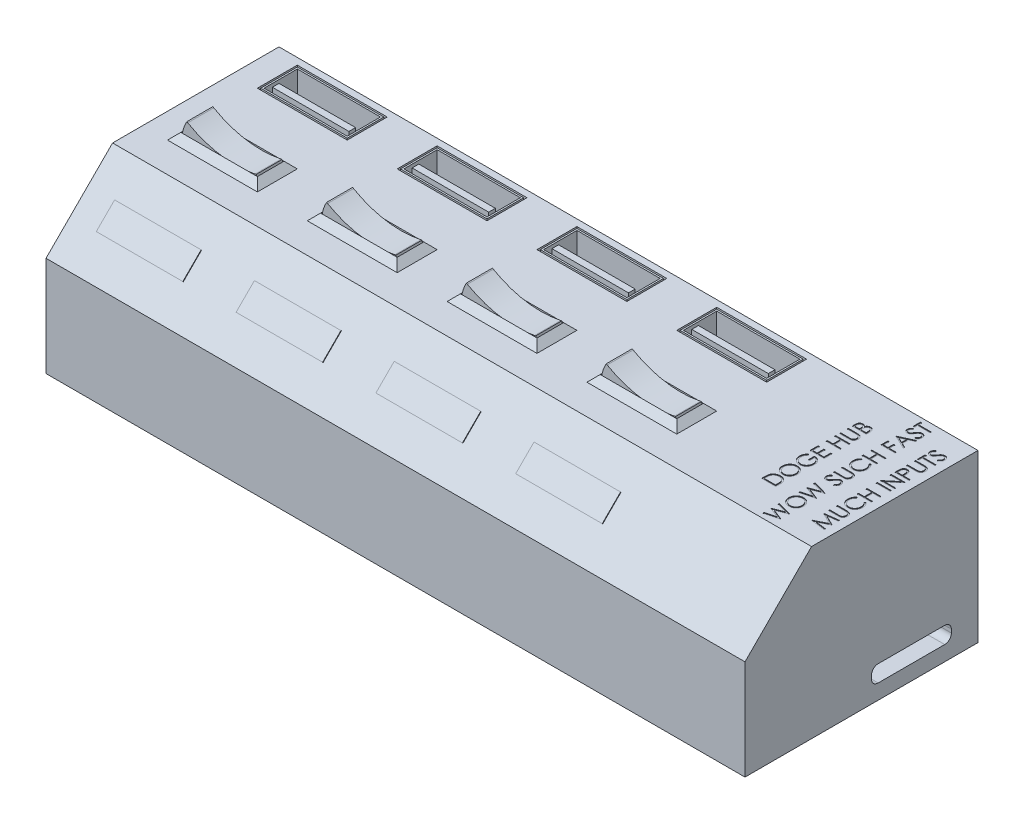
SolidWorks part; units mm, degrees
ref_plane "Plano frontal" through (0, 0, 0) normal (0, 0, 1) x (1, 0, 0)
ref_plane "Plano superior" through (0, 0, 0) normal (0, 1, 0) x (1, 0, 0)
ref_plane "Plano direito" through (0, 0, 0) normal (1, 0, 0) x (0, 0, -1)
sketch "Esboço1" plane through (0, 0, 0) normal (0, 1, 0) x (1, 0, 0)
  line L1 (52.5, -17.5) -> (-52.5, -17.5)
  line L2 (52.5, -17.5) -> (52.5, 17.5)
  line L3 (52.5, 17.5) -> (-52.5, 17.5)
  line L4 (-52.5, -17.5) -> (-52.5, 17.5)
  line L5 (52.5, -17.5) -> (-52.5, 17.5) construction
  line L6 (52.5, 17.5) -> (-52.5, -17.5) construction
  point P0 (0, 0)
  dimension "D1" = 35
  dimension "D2" = 105
extrude "Ressalto-extrusão1" add sketch "Esboço1" along normal blind 25
chamfer "Chanfro1" distance 10 angle 45 1 edges at (0, 25, 17.5)
sketch "Esboço2" plane through (0, 25, 0) normal (0, 1, 0) x (1, 0, 0)
  line L0 (0, 17.5) -> (0, 13.5) construction
  line L1 (52.5, 17.5) -> (-52.5, 17.5) construction
  line L2 (0, 13.5) -> (0, 3) construction
  line L3 (0, 3) -> (0, -7.5) construction
  line L4 (-52.5, -7.5) -> (52.5, -7.5) construction
  line L5 (-52.5, 13.5) -> (52.5, 13.5) construction
  line L6 (-52.5, 17.5) -> (-52.5, -7.5) construction
  line L7 (52.5, -7.5) -> (52.5, 17.5) construction
  line L8 (-52.5, 3) -> (52.5, 3) construction
  line L9 (-52.5, 0) -> (-42, 0) construction
  line L10 (-42, 0) -> (-21, 0) construction
  line L11 (-21, 0) -> (0, 0) construction
  line L12 (0, 0) -> (21, 0) construction
  line L13 (21, 0) -> (42, 0) construction
  line L14 (42, 0) -> (52.5, 0) construction
  line L15 (-42, -7.5) -> (-42, 17.5) construction
  line L16 (-21, 17.5) -> (-21, -7.5) construction
  line L17 (21, 17.5) -> (21, -7.5) construction
  line L18 (42, 17.5) -> (42, -7.5) construction
  line L19 (-48.75, 10.5) -> (-35.25, 10.5)
  line L20 (-48.75, 10.5) -> (-48.75, 16.5)
  line L21 (-48.75, 16.5) -> (-35.25, 16.5)
  line L22 (-35.25, 10.5) -> (-35.25, 16.5)
  line L23 (-48.75, 10.5) -> (-35.25, 16.5) construction
  line L24 (-48.75, 16.5) -> (-35.25, 10.5) construction
  line L25 (-27.75, 16.5) -> (-14.25, 16.5)
  line L26 (-27.75, 16.5) -> (-27.75, 10.5)
  line L27 (-27.75, 10.5) -> (-14.25, 10.5)
  line L28 (-14.25, 16.5) -> (-14.25, 10.5)
  line L29 (-27.75, 16.5) -> (-14.25, 10.5) construction
  line L30 (-27.75, 10.5) -> (-14.25, 16.5) construction
  line L31 (-6.75, 16.5) -> (6.75, 16.5)
  line L32 (-6.75, 16.5) -> (-6.75, 10.5)
  line L33 (-6.75, 10.5) -> (6.75, 10.5)
  line L34 (6.75, 16.5) -> (6.75, 10.5)
  line L35 (-6.75, 16.5) -> (6.75, 10.5) construction
  line L36 (-6.75, 10.5) -> (6.75, 16.5) construction
  line L37 (14.25, 16.5) -> (27.75, 16.5)
  line L38 (14.25, 16.5) -> (14.25, 10.5)
  line L39 (14.25, 10.5) -> (27.75, 10.5)
  line L40 (27.75, 16.5) -> (27.75, 10.5)
  line L41 (14.25, 16.5) -> (27.75, 10.5) construction
  line L42 (14.25, 10.5) -> (27.75, 16.5) construction
  line L43 (-48.5, 16.25) -> (-35.5, 16.25)
  line L44 (35.25, 16.5) -> (48.75, 16.5) construction
  line L45 (35.25, 16.5) -> (35.25, 10.5) construction
  line L46 (35.25, 10.5) -> (48.75, 10.5) construction
  line L47 (48.75, 16.5) -> (48.75, 10.5) construction
  line L48 (35.25, 16.5) -> (48.75, 10.5) construction
  line L49 (35.25, 10.5) -> (48.75, 16.5) construction
  line L50 (-35.5, 10.75) -> (-35.5, 16.25)
  line L51 (-48.5, 10.75) -> (-35.5, 10.75)
  line L52 (-48.5, 10.75) -> (-48.5, 16.25)
  line L53 (-27.5, 16.25) -> (-14.5, 16.25)
  line L54 (-14.5, 16.25) -> (-14.5, 10.75)
  line L55 (-27.5, 10.75) -> (-14.5, 10.75)
  line L56 (-27.5, 16.25) -> (-27.5, 10.75)
  line L57 (-6.5, 16.25) -> (6.5, 16.25)
  line L58 (6.5, 16.25) -> (6.5, 10.75)
  line L59 (-6.5, 10.75) -> (6.5, 10.75)
  line L60 (-6.5, 16.25) -> (-6.5, 10.75)
  line L61 (14.5, 16.25) -> (27.5, 16.25)
  line L62 (27.5, 16.25) -> (27.5, 10.75)
  line L63 (14.5, 10.75) -> (27.5, 10.75)
  line L64 (14.5, 16.25) -> (14.5, 10.75)
  line L65 (-48.25, 16) -> (-35.75, 16)
  line L66 (-47.75, 11.75) -> (-36.25, 11.75)
  line L67 (-47.75, 11.75) -> (-47.75, 12.75)
  line L68 (-47.75, 12.75) -> (-36.25, 12.75)
  line L69 (-36.25, 11.75) -> (-36.25, 12.75)
  line L70 (-47.75, 11.75) -> (-36.25, 12.75) construction
  line L71 (-47.75, 12.75) -> (-36.25, 11.75) construction
  line L72 (-35.75, 11) -> (-35.75, 16)
  line L73 (-48.25, 11) -> (-35.75, 11)
  line L74 (-48.25, 11) -> (-48.25, 16)
  line L75 (-27.25, 16) -> (-14.75, 16)
  line L76 (-14.75, 16) -> (-14.75, 11)
  line L77 (-27.25, 11) -> (-14.75, 11)
  line L78 (-27.25, 16) -> (-27.25, 11)
  line L79 (-6.25, 16) -> (6.25, 16)
  line L80 (6.25, 16) -> (6.25, 11)
  line L81 (-6.25, 11) -> (6.25, 11)
  line L82 (-6.25, 16) -> (-6.25, 11)
  line L83 (14.75, 16) -> (27.25, 16)
  line L84 (27.25, 16) -> (27.25, 11)
  line L85 (14.75, 11) -> (27.25, 11)
  line L86 (14.75, 16) -> (14.75, 11)
  line L87 (-26.75, 12.75) -> (-15.25, 12.75)
  line L88 (-26.75, 11.75) -> (-15.25, 11.75)
  line L89 (-26.75, 11.75) -> (-26.75, 12.75)
  line L90 (-15.25, 11.75) -> (-15.25, 12.75)
  line L91 (-5.75, 12.75) -> (5.75, 12.75)
  line L92 (-5.75, 11.75) -> (5.75, 11.75)
  line L93 (-5.75, 11.75) -> (-5.75, 12.75)
  line L94 (5.75, 11.75) -> (5.75, 12.75)
  line L95 (15.25, 12.75) -> (26.75, 12.75)
  line L96 (15.25, 11.75) -> (26.75, 11.75)
  line L97 (15.25, 11.75) -> (15.25, 12.75)
  line L98 (26.75, 11.75) -> (26.75, 12.75)
  point P30 (-42, 13.5)
  point P35 (0, 13.5)
  point P37 (-21, 13.5)
  point P45 (21, 13.5)
  point P52 (42, 13.5)
  point P73 (-42, 12.25)
  dimension "D1" = 4
  dimension "D2" = 13.5
  dimension "D3" = 6
  dimension "D4" = 7.5
  dimension "D5" = 0.25
  dimension "D6" = 1
  dimension "D7" = 1
  dimension "D8" = 11.5
  dimension "D11" = 9.5
  dimension "D9" = 0.25
  dimension "D10" = 4
extrude "Corte-extrusão1" cut sketch "Esboço2" against normal blind 15 contours L74 L73 L72 L65 L69 L66 L67 L68 | L19 L22 L21 L20 L51 L52 L43 L50 | L28 L25 L26 L27 L56 L53 L54 L55 | L75 L78 L77 L76 L90 L88 L89 L87 | L34 L31 L32 L33 L60 L57 L58 L59 | L79 L82 L81 L80 L94 L92 L93 L91 | L40 L37 L38 L39 L64 L61 L62 L63 | L83 L86 L85 L84 L98 L96 L97 L95 region at (-48.6023, 25, -13.5) region at (-21, 25, -16.3523) region at (0, 25, -16.3523) region at (21, 25, -16.3523) region at (-42, 25, -13.7819) region at (-21, 25, -13.7819) region at (0, 25, -13.7819) region at (21, 25, -13.7819)
sketch "Esboço3" plane through (0, 25, 0) normal (0, 1, 0) x (1, 0, 0)
  line L0 (-35.25, 10.5) -> (-35.25, 16.5) construction
  line L1 (-48.75, 3) -> (-35.25, 3)
  line L2 (-48.75, 3) -> (-48.75, -3)
  line L3 (-48.75, -3) -> (-35.25, -3)
  line L4 (-35.25, 3) -> (-35.25, -3)
  line L5 (-48.75, 3) -> (-35.25, -3) construction
  line L6 (-48.75, -3) -> (-35.25, 3) construction
  line L7 (-48.75, 16.5) -> (-35.25, 16.5) construction
  point P0 (-42, 0)
extrude "Ressalto-extrusão2" add sketch "Esboço3" along normal blind 1 draft 45
sketch "Esboço4" plane through (0, 26, 0) normal (0, 1, 0) x (1, 0, 0)
  line L1 (-47.75, -2) -> (-36.25, -2)
  line L2 (-47.75, -2) -> (-47.75, 2)
  line L3 (-47.75, 2) -> (-36.25, 2)
  line L4 (-36.25, -2) -> (-36.25, 2)
  line L5 (-47.75, -2) -> (-36.25, 2) construction
  line L6 (-47.75, 2) -> (-36.25, -2) construction
  point P0 (-42, 0)
extrude "Corte-extrusão2" cut sketch "Esboço4" against normal blind 1
ref_plane "Plano1" through (0, 0, 0) normal (0, 0, 1) x (1, 0, 0)
sketch "Esboço5" plane through (0, 0, 0) normal (0, 0, 1) x (1, 0, 0)
  line L0 (-47.65, 25) -> (-36.35, 25)
  line L2 (-47.65, 25) -> (-47.75, 25) construction
  line L3 (-48.75, 25) -> (-35.25, 25) construction
  line L4 (-46.8931, 27.8) -> (-46.7538, 27.7196)
  line L5 (-36.6307, 26.1163) -> (-36.4734, 26.1497)
  line L6 (-36.35, 25) -> (-36.25, 25) construction
  arc A0 (-47.65, 25) -> (-46.8931, 27.8) centre (-42, 24.975) cw
  arc A1 (-36.4734, 26.1497) -> (-36.35, 25) centre (-42, 24.975) cw
  arc A2 (-36.6307, 26.1163) -> (-46.7538, 27.7196) centre (-39.6038, 40.1038) cw
  point P7 (-42, 25)
  dimension "D4" = 14.3
  dimension "D1" = 0.1
  dimension "D2" = 30
  dimension "D3" = 12
  dimension "D5" = 2.8
extrude "Ressalto-extrusão3" add sketch "Esboço5" along normal mid plane 3.9
sketch "Esboço6" plane through (0, 16.25, 16.25) normal (0, 0.7071, 0.7071) x (1, 0, 0)
  line L0 (-42, 12.3744) -> (-42, -1.7678) construction
  line L1 (52.5, -1.7678) -> (-52.5, -1.7678) construction
  line L2 (-21, 12.3744) -> (-21, -1.7678) construction
  line L3 (0, 12.3744) -> (0, -1.7678) construction
  line L4 (21, 12.3744) -> (21, -1.7678) construction
  line L5 (-35.5, 25.2791) -> (-35.5, 29.1682) construction
  line L6 (-48.5, 7.2478) -> (-35.5, 7.2478)
  line L7 (-48.5, 7.2478) -> (-48.5, 3.3588)
  line L8 (-48.5, 3.3588) -> (-35.5, 3.3588)
  line L9 (-35.5, 7.2478) -> (-35.5, 3.3588)
  line L10 (-48.5, 7.2478) -> (-35.5, 3.3588) construction
  line L11 (-48.5, 3.3588) -> (-35.5, 7.2478) construction
  line L12 (-48.5, 25.2791) -> (-35.5, 25.2791) construction
  point P14 (-42, 5.3033)
extrude "Ressalto-extrusão4" add sketch "Esboço6" along normal blind 0.1
pattern_linear "Padrão linear1" count 4 spacing 21 along (1, 0, 0) of "Ressalto-extrusão2", "Corte-extrusão2", "Ressalto-extrusão3", "Ressalto-extrusão4"
sketch "Esboço8" plane through (0, 25, 0) normal (0, 1, 0) x (1, 0, 0)
  text T0 "DOGE HUB\r\nWOW SUCH FAST\r\nMUCH INPUTS" font "Century Gothic" height in points 8
extrude "Corte-extrusão3" cut sketch "Esboço8" against normal blind 0.1
sketch "Esboço9" plane through (52.5, 0, 0) normal (1, 0, 0) x (0, 0, -1)
  line L0 (-17.5, 0) -> (17.5, 0) construction
  line L1 (2.5, 4.75) -> (12.5, 4.75)
  line L2 (1.5, 3.75) -> (1.5, 3.25)
  line L3 (2.5, 2.25) -> (12.5, 2.25)
  line L4 (13.5, 3.75) -> (13.5, 3.25)
  line L5 (1.5, 4.75) -> (13.5, 2.25) construction
  line L6 (1.5, 2.25) -> (13.5, 4.75) construction
  line L7 (17.5, 25) -> (17.5, 0) construction
  arc A0 (1.5, 3.25) -> (2.5, 2.25) centre (2.5, 3.25) ccw
  arc A1 (12.5, 2.25) -> (13.5, 3.25) centre (12.5, 3.25) ccw
  arc A2 (12.5, 4.75) -> (13.5, 3.75) centre (12.5, 3.75) cw
  arc A3 (2.5, 4.75) -> (1.5, 3.75) centre (2.5, 3.75) ccw
  point P0 (7.5, 3.5)
  dimension "D5" = 1
  dimension "D1" = 12
  dimension "D2" = 2.5
  dimension "D3" = 3.5
  dimension "D4" = 4
extrude "Corte-extrusão4" cut sketch "Esboço9" against normal blind 10
